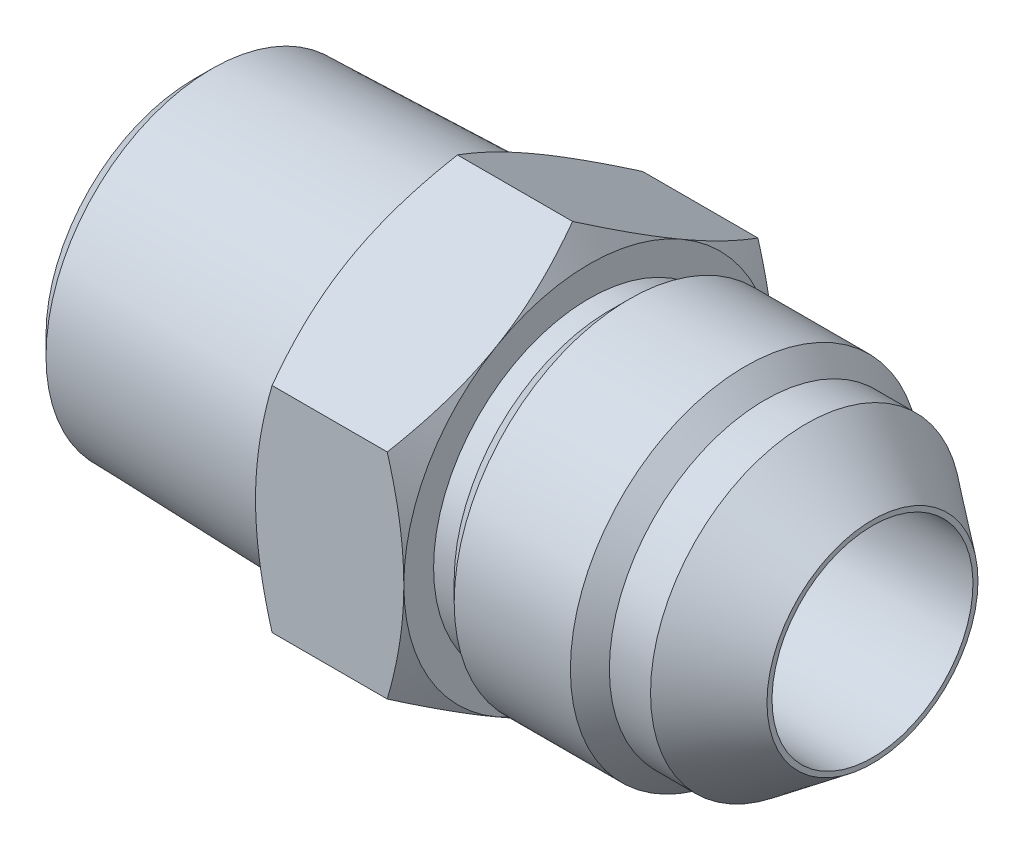
SolidWorks part; units mm, degrees
material "AISI 316 Stainless Steel Sheet (SS)"
ref_plane "Front" through (0, 0, 0) normal (0, 0, 1) x (1, 0, 0)
ref_plane "Top" through (0, 0, 0) normal (0, 1, 0) x (1, 0, 0)
ref_plane "Right" through (0, 0, 0) normal (1, 0, 0) x (0, 0, -1)
sketch "Sketch6" plane through (0, 0, 0) normal (0, 0, 1) x (1, 0, 0)
  line L0 (-7.112, 13.335) -> (-7.112, -13.335) construction
  line L1 (26.162, 13.4937) -> (26.162, -13.4937) construction
  line L2 (-26.162, 0) -> (26.162, 0)
  line L4 (-26.162, 0) -> (-26.162, 13.4938)
  line L5 (-26.162, 13.4938) -> (26.162, 13.4937)
  line L6 (26.162, 0) -> (26.162, 13.4937)
  line L7 (-26.162, 7.747) -> (-26.162, -7.747) construction
  line L8 (-7.112, 15.0495) -> (-7.112, -15.0495) construction
  line L9 (4.318, 15.0495) -> (4.318, -15.0495) construction
  point P4 (4.318, 0)
  point P6 (-7.112, 0)
  dimension "Straight Dia" = 26.9875
  dimension "Length" = 52.324
  dimension "L1" = 21.844
  dimension "Pipe OD" = 26.67
  dimension "L2" = 19.05
  dimension "D1" = 15.494
  dimension "D2" = 30.099
revolve "Revolve3" add sketch "Sketch6" angle 360 about L2
sketch "Sketch14" plane through (26.162, 0, 0) normal (-1, 0, 0) x (0, 0, 1)
  circle A1 centre (0, 0) radius 13.4938
  circle A2 centre (0, 0) radius 13.4938
  dimension "D1" = 0
curve "Helix/Spiral1" pitch 2.1167 height 23.9607 turns 11.32 parameters "Pitch"=2.1167
sketch "Sketch15" plane through (0, 0, 0) normal (0, 0, 1) x (1, 0, 0)
  line L0 (26.162, 13.4938) -> (28.0141, 13.4938)
  line L1 (28.0141, 13.4938) -> (27.2203, 12.1189)
  line L2 (27.2203, 12.1189) -> (26.9557, 12.1189)
  line L3 (26.9557, 12.1189) -> (26.162, 13.4938)
  line L4 (27.088, 12.1189) -> (27.088, 13.4938) construction
  line L5 (26.5589, 12.8063) -> (27.6172, 12.8063) construction
  dimension "D1" = 60
  dimension "D2" = 0.2646
  dimension "D3" = 1.0583
sweep "Cut-Sweep1" [suppressed] cut profiles "Sketch15" path "Helix/Spiral1"
ref_plane "Plane1" through (-7.112, 0, 0) normal (1, 0, 0) x (0, 0, -1)
sketch "Sketch12" plane through (-7.112, 0, 0) normal (1, 0, 0) x (0, 0, -1)
  line L1 (0, 16.4978) -> (-14.2875, 8.2489)
  line L2 (-14.2875, 8.2489) -> (-14.2875, -8.2489)
  line L3 (-14.2875, -8.2489) -> (0, -16.4978)
  line L4 (0, -16.4978) -> (14.2875, -8.2489)
  line L5 (14.2875, -8.2489) -> (14.2875, 8.2489)
  line L6 (14.2875, 8.2489) -> (0, 16.4978)
  circle A0 centre (0, 0) radius 14.2875 construction
  dimension "Hex" = 28.575
extrude "Extrude1" add sketch "Sketch12" along normal up to vertex (11.43 mm away) up to point (4.318, 0, 0)
sketch "Sketch7" plane through (0, 0, 0) normal (0, 0, 1) x (1, 0, 0)
  line L0 (-26.162, 0) -> (-26.162, 7.747)
  line L2 (-26.162, 7.747) -> (26.162, 7.747)
  line L4 (26.162, 0) -> (26.162, 13.4937) construction
  line L11 (26.162, 7.747) -> (26.162, 0)
  line L12 (26.162, 0) -> (-26.162, 0)
  line L13 (-26.162, 7.747) -> (-26.162, -7.747) construction
  dimension "ID" = 15.494
sketch "Sketch10" plane through (0, 0, 0) normal (0, 0, 1) x (1, 0, 0)
  line L0 (-26.162, 13.4938) -> (26.162, 13.4937) construction
  line L1 (26.162, 13.4938) -> (28.0141, 13.4938) construction
  line L2 (-7.112, -13.335) -> (-26.162, -12.7529) construction
  line L3 (4.318, 16.4978) -> (4.318, 8.2489) construction
  line L5 (0, 0) -> (-26.162, 0) construction
  line L6 (7.4073, 13.4937) -> (4.318, 13.4937)
  line L9 (4.318, 11.9919) -> (4.318, 13.4937)
  line L21 (26.162, 13.4937) -> (16.366, 13.4937)
  line L22 (16.366, 13.4937) -> (17.8678, 11.9919)
  line L23 (17.8678, 11.9919) -> (21.0428, 11.9919)
  line L24 (21.0428, 11.9919) -> (26.162, 8.1344)
  line L25 (26.162, 8.1344) -> (26.162, 13.4937)
  line L26 (5.9055, 11.9919) -> (4.318, 11.9919)
  line L27 (7.4073, 13.4937) -> (5.9055, 11.9919)
  point P5 (13.6345, -13.4937)
  point P9 (-17.9977, -13.0024)
  dimension "D1" = 16.2687
  dimension "D2" = 37
  dimension "D3" = 3.175
  dimension "D5" = 45
  dimension "D4" = 1.5875
  dimension "D6" = 4.2333
  dimension "D7" = 0.127
  dimension "D9" = 8.1643
  dimension "D8" = 1.75
revolve "Cut-Revolve6" cut sketch "Sketch10" angle 360 about L2
revolve "Cut-Revolve5" cut sketch "Sketch7" angle 360 about L12
sketch "Sketch13" plane through (0, 0, 0) normal (0, 0, 1) x (1, 0, 0)
  line L0 (-7.112, 16.4978) -> (-7.112, 14.2875)
  line L1 (-7.112, 8.2489) -> (-7.112, 16.4978) construction
  line L2 (-7.112, 14.2875) -> (-5.8359, 16.4978)
  line L3 (-5.8359, 16.4978) -> (-7.112, 16.4978)
  line L4 (3.0419, 16.4978) -> (4.318, 14.2875)
  line L5 (4.318, 16.4978) -> (4.318, 8.2489) construction
  line L6 (4.318, 14.2875) -> (4.318, 16.4978)
  line L7 (4.318, 16.4978) -> (3.0419, 16.4978)
  dimension "D2" = 30
revolve "Cut-Revolve7" cut sketch "Sketch13" angle 360 about L2
sketch "Sketch17" plane through (-26.162, 0, 0) normal (-1, 0, 0) x (0, 0, 1)
  circle A0 centre (0, 0) radius 13.4938 construction
  circle A1 centre (0, 0) radius 13.4938
extrude "Cut-Extrude1" cut sketch "Sketch17" against normal up to vertex (19.05 mm away) up to point (-7.112, 0, 0)
ref_plane "Plane2" through (-7.112, 0, 0) normal (1, 0, 0) x (0, 0, -1)
sketch "Sketch19" plane through (-7.112, 0, 0) normal (1, 0, 0) x (0, 0, -1)
  circle A0 centre (0, 0) radius 13.335
extrude "Boss-Extrude1" add sketch "Sketch19" against normal up to vertex (19.05 mm away) draft 1.75 separate body up to point (-26.162, 0, 0)
sketch "Sketch20" plane through (-26.162, 0, 0) normal (1, 0, 0) x (0, 0, -1)
  circle A1 centre (0, 0) radius 12.753
  circle A2 centre (0, 0) radius 12.753 construction
sketch "Sketch21" plane through (0, 0, 0) normal (0, 0, 1) x (1, 0, 0)
  line L0 (-27.7682, 12.6329) -> (-26.2313, 12.6329) construction
  line L1 (-27.9069, 12.8731) -> (-26.9998, 11.3019) construction
  line L2 (-27.1199, 11.5099) -> (-26.8797, 11.5099)
  line L3 (-26.9998, 11.3019) -> (-26.0927, 12.8731) construction
  line L4 (-26.9998, 11.3019) -> (-26.8797, 11.5099) construction
  line L5 (-26.9998, 12.6329) -> (-26.9998, 12.8731) construction
  line L6 (-27.9069, 12.8731) -> (-26.0927, 12.8731) construction
  line L7 (-26.9998, 12.753) -> (-26.162, 12.753) construction
  line L8 (-26.0927, 12.8731) -> (-27.8376, 12.753)
  line L9 (-27.8376, 12.753) -> (-27.1199, 11.5099)
  line L10 (-26.8797, 11.5099) -> (-26.0927, 12.8731)
  line L11 (-26.9998, 11.3019) -> (-26.9998, 11.5099) construction
  dimension "D2" = 0.2402
  dimension "D1" = 1.8143
curve "Helix/Spiral2" parameters "Pitch"=1.8143
chamfer "Chamfer1" distance 1.3607 angle 45 1 edges at (-26.162, 0, -12.753) first distance on face at (-26.162, 0, -12.753)
sketch "Sketch22" plane through (-7.112, 0, 0) normal (1, 0, 0) x (0, 0, -1)
  circle A1 centre (0, 0) radius 13.335
  circle A2 centre (0, 0) radius 13.335
  dimension "D1" = 0
sweep "Cut-Sweep2" [suppressed] cut profiles "Sketch21" path "Helix/Spiral2"
extrude "Boss-Extrude3" add sketch "Sketch22" against normal up to vertex (19.05 mm away) draft 15 up to point (-26.162, 13.4938, 0)
combine bodies "Combine1" operation type add bodies to combine 173 169
sketch "Sketch23" plane through (-26.162, 0, 0) normal (-1, 0, 0) x (0, 0, 1)
  circle A2 centre (0, 0) radius 7.747
extrude "Cut-Extrude2" cut sketch "Sketch23" against normal up to vertex (19.05 mm away) up to point (-7.112, 0, 0)
equation "\"D3@Helix/Spiral1\" = \"L1@Sketch6\"+\"Pitch@Helix/Spiral1\""
equation "\"D2@Sketch15\" = \"Pitch@Helix/Spiral1\"*.125"
equation "\"D3@Sketch15\" = \"Pitch@Helix/Spiral1\"*.5"
equation "\"D3@Sketch10\" = \"Pitch@Helix/Spiral1\"*1.5"
equation "\"D1@Sketch10\" = \"ID@Sketch7\"*1.05"
equation "\"D1@Sketch21\" = \"Pitch@Helix/Spiral2\""
equation "\"D3@Helix/Spiral2\" = \"L2@Sketch6\"+\"Pitch@Helix/Spiral2\""
equation "\"D1@Chamfer1\" = \"Pitch@Helix/Spiral2\"*.75"
equation "\"D4@Sketch10\" = \"Pitch@Helix/Spiral1\"*.75"
equation "\"D6@Sketch10\" = \"Pitch@Helix/Spiral1\"*2"
equation "\"D9@Sketch10\" = \"Pitch@Helix/Spiral2\"*4.5"
equation "\"D2@Sketch6\" = \"Hex@Sketch12\"+.06"
